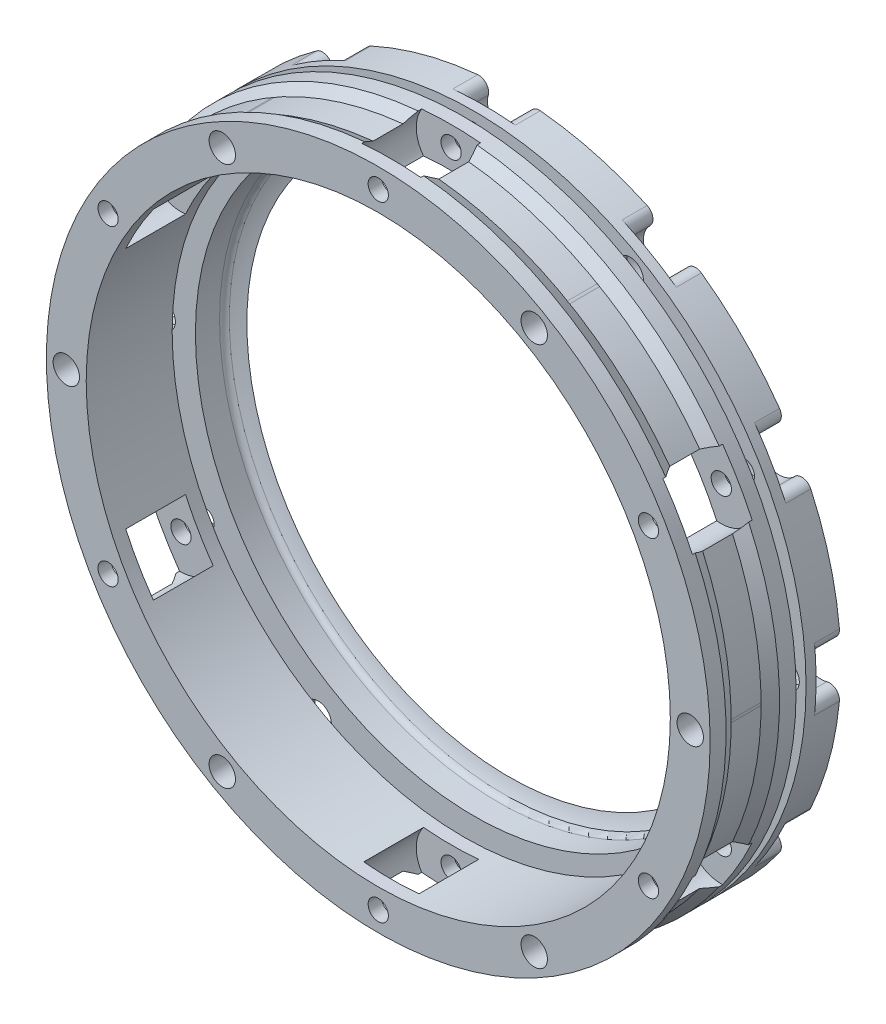
SolidWorks part; units mm, degrees
material "PUR"
ref_plane "Front Plane" through (0, 0, 0) normal (0, 0, 1) x (1, 0, 0)
ref_plane "Top Plane" through (0, 0, 0) normal (0, 1, 0) x (1, 0, 0)
ref_plane "Right Plane" through (0, 0, 0) normal (1, 0, 0) x (0, 0, -1)
sketch "Sketch1" plane through (0, 0, 0) normal (0, 0, 1) x (1, 0, 0)
  circle A0 centre (0, 0) radius 100 construction
  circle A1 centre (0, 0) radius 100
  circle A2 centre (0, 0) radius 88
  dimension "D1" = 12
extrude "Core Structure" add sketch "Sketch1" along normal up to surface (25.9 mm away)
ref_axis "Axis1" through (0, 0, 25.9) along (0, 0, -1)
ref_plane "Midplane" through (0, 0, 12.95) normal (0, 0, 1) x (1, 0, 0)
sketch "Sketch5" plane through (0, 0, -3) normal (0, 0, 1) x (1, 0, 0)
  circle A0 centre (0, 0) radius 100 construction
  circle A1 centre (0, 0) radius 88 construction
  circle A2 centre (0, 0) radius 100
  circle A3 centre (0, 0) radius 88 construction
  circle A4 centre (0, 0) radius 84
  dimension "D1" = 4
extrude "Hover Brim" add sketch "Sketch5" against normal blind 10.5 separate body
sketch "Sketch3" plane through (0, 0, 12.95) normal (0, 0, 1) x (1, 0, 0)
  circle A0 centre (0, 94) radius 3 construction
  circle A1 centre (0, 94) radius 3 construction
  circle A2 centre (0, 94) radius 10.5
  dimension "D1" = 21
extrude "Bearing Hole" cut sketch "Sketch3" against normal mid plane 18
sketch "Sketch6" plane through (0, 0, 21.95) normal (0, 0, -1) x (-1, 0, 0)
  circle A0 centre (0, 94) radius 3.05
  arc A4 (-8.8788, 99.6051) -> (-8.3279, 87.6051) centre (0, 94) ccw
  arc A5 (8.3279, 87.6051) -> (-8.3279, 87.6051) centre (0, 0) ccw
  arc A6 (8.3279, 87.6051) -> (8.8788, 99.6051) centre (0, 94) ccw
  arc A7 (8.8788, 99.6051) -> (-8.8788, 99.6051) centre (0, 0) ccw
  arc A8 (-8.8788, 99.6051) -> (-8.3279, 87.6051) centre (0, 94) ccw construction
  arc A9 (8.3279, 87.6051) -> (-8.3279, 87.6051) centre (0, 0) ccw construction
  arc A10 (8.3279, 87.6051) -> (8.8788, 99.6051) centre (0, 94) ccw construction
  arc A11 (8.8788, 99.6051) -> (-8.8788, 99.6051) centre (0, 0) ccw construction
  dimension "D2" = 6.1
  dimension "D1" = 0
extrude "Bearing Mounting Hole" cut sketch "Sketch6" against normal through all both and the other way through all
sketch "Sketch2" plane through (0, 0, 25.9) normal (0, 0, 1) x (1, 0, 0)
  circle A0 centre (47, 81.4064) radius 3.9751 construction
  circle A1 centre (47, 81.4064) radius 3.9751
extrude "Structural Hole" cut sketch "Sketch2" against normal through all both and the other way through all
pattern_circular "CirPattern1" count 6 over 360 about axis through (0, 0, 25.9) along (0, 0, -1) of "Bearing Hole", "Structural Hole", "Bearing Mounting Hole" reverse direction yes
sketch "Sketch7" plane through (0, 0, -13.5) normal (0, 0, -1) x (-1, 0, 0)
  circle A0 centre (-47, 81.4064) radius 6.5
  circle A1 centre (0, 94) radius 6.5
  dimension "D1" = 13
  dimension "D2" = 13
extrude "Cut-Extrude5" cut sketch "Sketch7" against normal blind 7.5
fillet "Fillet2" radius 3 4 edges at (2.5783, 99.9668, -9.75) (-2.5783, 99.9668, -9.75) (52.2163, 85.2846, -9.75) (47.7505, 87.8629, -9.75)
sketch "Sketch4" plane through (0, 0, 0) normal (0, 1, 0) x (1, 0, 0)
  line L0 (99, -8.55) -> (-99, -8.55) construction
  line L1 (99, -8.55) -> (-99, -8.55) construction
  line L2 (-99, -17.55) -> (99, -17.55) construction
  line L3 (-99, -17.55) -> (99, -17.55) construction
  line L4 (-100, 0) -> (-100, -25.9) construction
  line L5 (-100, 0) -> (-100, -25.9) construction
  line L7 (-98, -17.55) -> (-98, -8.55)
  line L9 (-98, -17.55) -> (-100, -21.1)
  line L10 (-100, -21.1) -> (-100, -5)
  line L11 (-100, -5) -> (-98, -8.55)
  line L12 (-98, -13.05) -> (-100, -13.05) construction
  line L13 (0, 0) -> (0, -45.0086) construction
  dimension "D1" = 5
  dimension "D2" = 1
revolve "Cut-Revolve1" cut sketch "Sketch4" angle 360 about L13
pattern_circular "CirPattern13" count 6 over 360 about axis through (0, 0, 25.9) along (0, 0, -1) of "Cut-Extrude5", "Fillet2"
sketch "Sketch8" plane through (0, 0, 0) normal (0, 1, 0) x (1, 0, 0)
  line L0 (84, 13.5) -> (-84, 13.5) construction
  line L1 (84, 13.5) -> (-84, 13.5) construction
  line L2 (84, 13.5) -> (79, 13.5)
  line L3 (84, 13.5) -> (84, 11.5)
  line L4 (84, 3) -> (84, 13.5) construction
  line L5 (79, 13.5) -> (75.9519, 14.3167) construction
  arc A0 (84, 11.5) -> (79, 13.5) centre (73.1155, -8.4612) ccw
  dimension "D1" = 2
  dimension "D2" = 5
  dimension "D3" = 15
revolve "Revolve1" add sketch "Sketch8" angle 360 about axis through (0, 0, 25.9) along (0, 0, -1)
fillet "Fillet3" radius 2 1 edges at (84, 0, -11.5)
